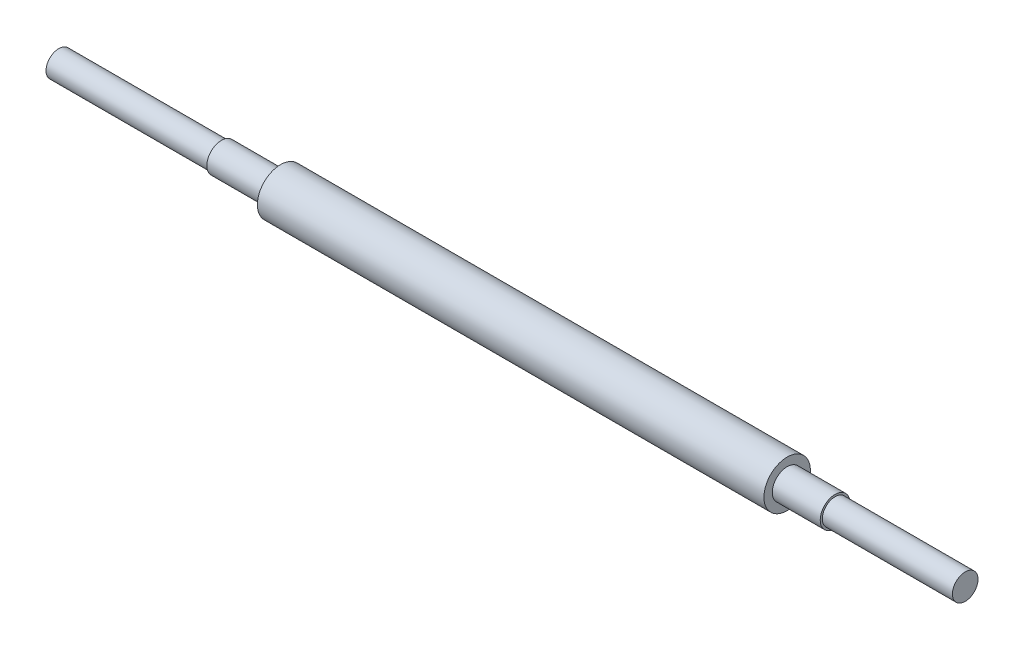
SolidWorks part; units mm, degrees
ref_plane "Front Plane" through (0, 0, 0) normal (0, 0, 1) x (1, 0, 0)
ref_plane "Top Plane" through (0, 0, 0) normal (0, 1, 0) x (1, 0, 0)
ref_plane "Right Plane" through (0, 0, 0) normal (1, 0, 0) x (0, 0, -1)
sketch "Sketch1" plane through (0, 0, 0) normal (0, 1, 0) x (1, 0, 0)
  line L0 (-78.6306, 0) -> (169.0721, 0) construction
  line L1 (-78.6306, 0) -> (-78.6306, 3.5)
  line L2 (-78.6306, 3.5) -> (-34.1806, 3.5)
  line L3 (-34.1806, 3.5) -> (-34.1806, 4)
  line L4 (-34.1806, 4) -> (-18.0179, 4)
  line L5 (-18.0179, 4) -> (-18.0179, 6.35)
  line L6 (-18.0179, 6.35) -> (120.4121, 6.35)
  line L7 (120.4121, 6.35) -> (120.4121, 4.064)
  line L8 (120.4121, 4.064) -> (133.5121, 4.064)
  line L9 (133.5121, 4.064) -> (133.5121, 3.5)
  line L10 (133.5121, 3.5) -> (169.0721, 3.5)
  line L11 (169.0721, 3.5) -> (169.0721, 0)
  line L12 (-78.6306, 0) -> (169.0721, 0)
  line L13 (-97.9506, 0) -> (194.5593, 0) construction
  point P15 (0, 0)
  dimension "D1" = 7
  dimension "D2" = 8
  dimension "D3" = 8.128
  dimension "D4" = 7
  dimension "D5" = 44.45
  dimension "D6" = 16.1627
  dimension "D7" = 13.1
  dimension "D8" = 35.56
  dimension "D9" = 138.43
  dimension "D10" = 6.35
revolve "Revolve1" add sketch "Sketch1" angle 360 about L13
